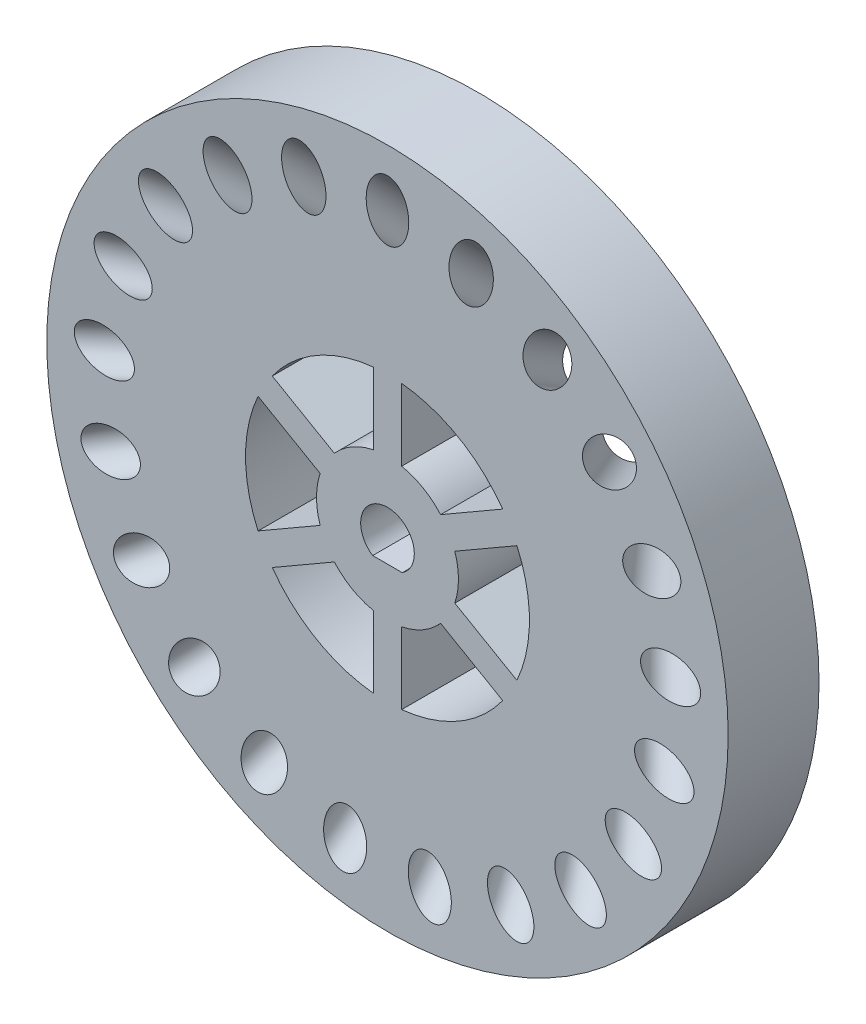
SolidWorks part; units mm, degrees
ref_plane "Front Plane" through (0, 0, 0) normal (0, 0, 1) x (1, 0, 0)
ref_plane "Top Plane" through (0, 0, 0) normal (0, 1, 0) x (1, 0, 0)
ref_plane "Right Plane" through (0, 0, 0) normal (1, 0, 0) x (0, 0, -1)
sketch "Sketch1" plane through (0, 0, 0) normal (0, 0, 1) x (1, 0, 0)
  line L0 (-1.6583, -2.5) -> (1.6583, -2.5)
  arc A0 (1.6583, -2.5) -> (-1.6583, -2.5) centre (0, 0) ccw
  circle A1 centre (0, 0) radius 38.1
  point P1 (0, 38.1)
  dimension "D1" = 6
  dimension "D2" = 76.2
  dimension "D3" = 2.5
extrude "Boss-Extrude1" add sketch "Sketch1" along normal blind 10.16
sketch "Sketch3" plane through (0, 0, 0) normal (1, 0, 0) x (0, 0, -1)
  line L0 (-10.16, 21.59) -> (0, 31.75)
  line L1 (0, 31.75) -> (0, 21.59)
  line L2 (0, 21.59) -> (-10.16, 21.59)
  point P0 (-10.16, 0)
  point P4 (-5.08, 26.67)
  dimension "D1" = 10.16
  dimension "D2" = 10.16
  dimension "D3" = 45
  dimension "D4" = 26.67
ref_plane "Plane1" through (0, 15.875, 15.875) normal (0, -0.7071, -0.7071) x (0, 0.7071, -0.7071)
sketch "Sketch5" plane through (0, 15.875, 15.875) normal (0, -0.7071, -0.7071) x (0, 0.7071, -0.7071)
  circle A0 centre (15.2664, 0) radius 2.3813
  dimension "D1" = 4.7625
extrude "Cut-Extrude1" cut sketch "Sketch5" against normal through all both and the other way through all
pattern_circular "CirPattern1" count 21 every 17.143 about axis through (0, 0, 10.16) along (0, 0, -1) of "Cut-Extrude1"
sketch "Sketch6" plane through (0, 0, 0) normal (0, 0, -1) x (-1, 0, 0)
  line L0 (-1.5875, 7.7771) -> (-1.5875, 15.7954)
  line L1 (1.5875, 15.7954) -> (1.5875, 7.7771)
  line L2 (5.9414, 5.2634) -> (12.8855, 9.2725)
  line L3 (14.473, 6.5229) -> (7.5289, 2.5137)
  line L4 (7.5289, -2.5137) -> (14.473, -6.5229)
  line L5 (12.8855, -9.2725) -> (5.9414, -5.2634)
  line L6 (1.5875, -7.7771) -> (1.5875, -15.7954)
  line L7 (-1.5875, -15.7954) -> (-1.5875, -7.7771)
  line L8 (-5.9414, -5.2634) -> (-12.8855, -9.2725)
  line L9 (-14.473, -6.5229) -> (-7.5289, -2.5137)
  line L10 (-7.5289, 2.5137) -> (-14.473, 6.5229)
  line L11 (-12.8855, 9.2725) -> (-5.9414, 5.2634)
  arc A0 (-7.5289, 2.5137) -> (-7.5289, -2.5137) centre (0, 0) ccw
  arc A1 (-14.473, 6.5229) -> (-14.473, -6.5229) centre (0, 0) ccw
  arc A2 (-12.8855, -9.2725) -> (-1.5875, -15.7954) centre (0, 0) ccw
  arc A3 (-5.9414, -5.2634) -> (-1.5875, -7.7771) centre (0, 0) ccw
  arc A4 (1.5875, -7.7771) -> (5.9414, -5.2634) centre (0, 0) ccw
  arc A5 (1.5875, -15.7954) -> (12.8855, -9.2725) centre (0, 0) ccw
  arc A6 (14.473, -6.5229) -> (14.473, 6.5229) centre (0, 0) ccw
  arc A7 (7.5289, -2.5137) -> (7.5289, 2.5137) centre (0, 0) ccw
  arc A8 (5.9414, 5.2634) -> (1.5875, 7.7771) centre (0, 0) ccw
  arc A9 (12.8855, 9.2725) -> (1.5875, 15.7954) centre (0, 0) ccw
  arc A10 (-1.5875, 7.7771) -> (-5.9414, 5.2634) centre (0, 0) ccw
  arc A11 (-1.5875, 15.7954) -> (-12.8855, 9.2725) centre (0, 0) ccw
  point P31 (0, 0)
  dimension "D1" = 15.875
  dimension "D2" = 31.75
  dimension "D3" = 3.175
  dimension "D4" = 1.5875
  dimension "D5" = 6
extrude "Cut-Extrude2" cut sketch "Sketch6" against normal blind 18.288
sketch "Sketch8" plane through (0, 0, 0) normal (1, 0, 0) x (0, 0, -1)
  line L0 (-10.16, 38.1) -> (0.0087, 27.9313)
  line L1 (0.0087, 27.9313) -> (0.0087, 38.1)
  line L2 (0.0087, 38.1) -> (-10.16, 38.1)
  line L3 (-10.16, 0) -> (0, 0)
  dimension "D1" = 45
revolve "Cut-Revolve1" [suppressed] cut sketch "Sketch8" angle 360 about L3
